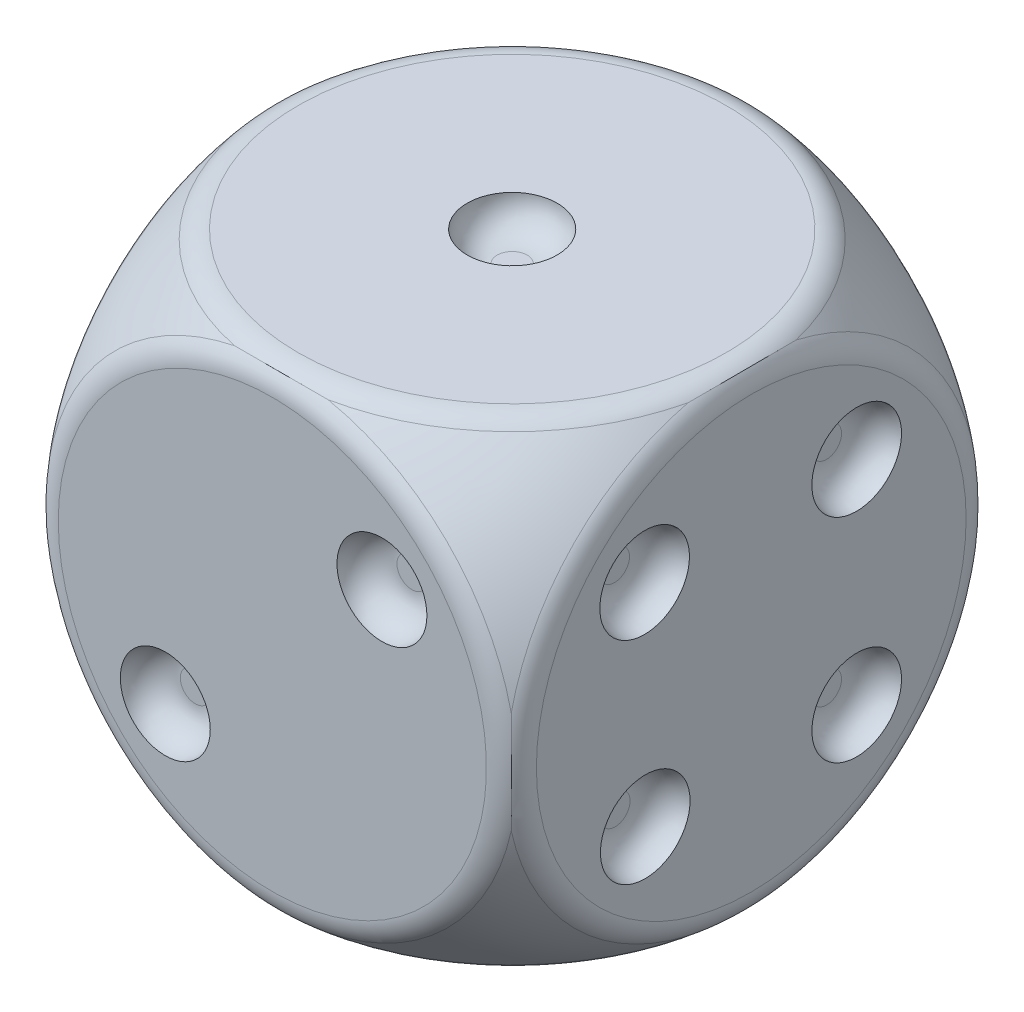
SolidWorks part; units mm, degrees
ref_plane "Front Plane" through (0, 0, 0) normal (0, 0, 1) x (1, 0, 0)
ref_plane "Top Plane" through (0, 0, 0) normal (0, 1, 0) x (1, 0, 0)
ref_plane "Right Plane" through (0, 0, 0) normal (1, 0, 0) x (0, 0, -1)
sketch "Sketch1" plane through (0, 0, 0) normal (0, 1, 0) x (1, 0, 0)
  line L1 (-7.9752, 8) -> (7.9255, 8.0001)
  line L2 (-7.9752, 8) -> (-8.0248, -7.9999)
  line L3 (-8.0248, -7.9999) -> (7.9752, -8)
  line L4 (7.9255, 8.0001) -> (7.9752, -8)
  line L5 (-7.9752, 8) -> (7.9752, -8) construction
  line L6 (-8.0248, -7.9999) -> (7.9255, 8.0001) construction
  point P0 (0, 0)
  dimension "D1" = 16
  dimension "D2" = 16
extrude "Boss-Extrude1" add sketch "Sketch1" along normal mid plane 16
sketch "Sketch2" plane through (0, 8, 0) normal (0, 1, 0) x (1, 0, 0)
  circle A0 centre (0, 0) radius 1.5
  dimension "D1" = 3
extrude "Cut-Extrude1" cut sketch "Sketch2" against normal blind 1 contours A0
sketch "Sketch4" plane through (0, 0, 8) normal (0, 0, 1) x (1, 0, 0)
  line L0 (-7.9752, -8) -> (7.9752, 8) construction
  circle A0 centre (-3.5715, -3.4992) radius 1.5
  circle A1 centre (3.6554, 3.4114) radius 1.5
  dimension "D3" = 3
  dimension "D4" = 3
  dimension "D1" = 5
  dimension "D2" = 5
sketch "Sketch5" plane through (-7.9999, 0, -0.0248) normal (-1, 0, -0.0031) x (-0.0031, 0, 1)
  line L0 (-7.9752, 8) -> (8.0248, -8) construction
  circle A0 centre (-3.5322, 3.5697) radius 1.5
  circle A1 centre (0.0321, 0.0632) radius 1.5
  circle A2 centre (3.5244, -3.515) radius 1.5
  dimension "D1" = 3
  dimension "D2" = 3
  dimension "D3" = 3
  dimension "D4" = 5
  dimension "D5" = 5
extrude "Cut-Extrude4" cut sketch "Sketch5" against normal blind 1
sketch "Sketch7" plane through (7.9502, 0, -0.0247) normal (1, 0, -0.0031) x (-0.0031, 0, -1)
  line L0 (-8.0247, 8) -> (7.9754, -8) construction
  line L1 (7.9754, 8) -> (-8.0247, -8) construction
  circle A0 centre (-3.5675, 3.5428) radius 1.5
  circle A1 centre (3.5282, -3.5529) radius 1.5
  circle A2 centre (3.5282, 3.5428) radius 1.5
  circle A3 centre (-3.5478, -3.5232) radius 1.5
  dimension "D1" = 3
  dimension "D2" = 3
  dimension "D3" = 3
  dimension "D4" = 3
  dimension "D5" = 5
  dimension "D6" = 5
extrude "Cut-Extrude6" cut sketch "Sketch7" against normal blind 1 contours A3 | A0 | A2 | A1
sketch "Sketch8" plane through (0, 0, -8) normal (0, 0, -1) x (-1, 0, 0)
  line L0 (-7.9751, 8) -> (8.0249, -8) construction
  line L1 (7.9751, 8) -> (-7.9255, -8) construction
  circle A0 centre (0, 0) radius 1.539
  circle A1 centre (-3.5281, 3.543) radius 1.5
  circle A2 centre (3.5369, -3.512) radius 1.5
  circle A3 centre (3.5369, 3.5341) radius 1.5
  circle A4 centre (-3.5281, -3.5751) radius 1.5
  dimension "D1" = 3
  dimension "D2" = 3
  dimension "D3" = 3
  dimension "D4" = 3
  dimension "D5" = 5
  dimension "D6" = 5
extrude "Cut-Extrude7" cut sketch "Sketch8" against normal blind 1 contours A1 | A3 | A0 | A4 | A2
sketch "Sketch9" plane through (0, -8, 0) normal (0, -1, 0) x (-1, 0, 0)
  line L0 (0.0248, -8) -> (0, 8) construction
  circle A0 centre (3.2248, -4) radius 1.5
  circle A1 centre (3.2248, 0) radius 1.5
  circle A2 centre (3.2248, 4) radius 1.5
  circle A3 centre (-3.1814, -3.9982) radius 1.5
  circle A5 centre (-3.1814, 4) radius 1.5
  circle A6 centre (-3.1814, 0) radius 1.5
  dimension "D1" = 3
  dimension "D2" = 3
  dimension "D3" = 3
  dimension "D4" = 3
  dimension "D5" = 3
  dimension "D6" = 3
  dimension "D7" = 3.2
  dimension "D8" = 4
  dimension "D9" = 4
extrude "Cut-Extrude9" cut sketch "Sketch9" against normal blind 1 contours A0 | A1 | A2 | A5 | A6 | A3
extrude "Cut-Extrude10" cut sketch "Sketch4" against normal blind 1 contours A1 | A0
sketch "Sketch11" plane through (0, 0, 0) normal (0, 0, 1) x (1, 0, 0)
  line L0 (11, 0) -> (16, 0)
  line L1 (-16, 0) -> (-11, 0)
  arc A0 (11, 0) -> (-11, 0) centre (0, 0) cw
  arc A1 (16, 0) -> (-16, 0) centre (0, 0) cw
  dimension "D1" = 11
  dimension "D2" = 5
revolve "Cut-Revolve2" cut sketch "Sketch11" angle 360 about L1
fillet "Fillet1" radius 1 6 edges at (7.9738, 0, 7.5775) (-7.9765, 0, -7.5747) (0, -8, 7.5498) (0, 8, 7.5498) (-7.5499, 0, 7.9999) (7.5498, 0, -8.0001)
fillet "Fillet2" radius 1 7 edges at (0, 7, 1.5) (6.9566, -3.5232, 2.0262) (6.9346, -3.5529, -5.0498) (6.9346, 3.5428, -5.0498) (6.9567, 3.5428, 2.0459) (5.1554, 3.4114, 7) (-2.0715, -3.4992, 7)
fillet "Fillet3" radius 1 14 edges at (3.1814, -7, 2.4982) (-3.2248, -7, 2.5) (-3.2248, -7, -1.5) (-3.2248, -7, -5.5) (3.1814, -7, -1.5) (-5.037, -3.512, -7) (-1.5391, 0, -7) (2.0281, 3.543, -7) (-6.9936, 3.5697, -2.054) (-7.0047, 0.0632, 1.5103) (-7.0155, -3.515, 5.0027) (3.1814, -7, -5.5) (2.0281, -3.5751, -7) (-5.037, 3.5341, -7)
